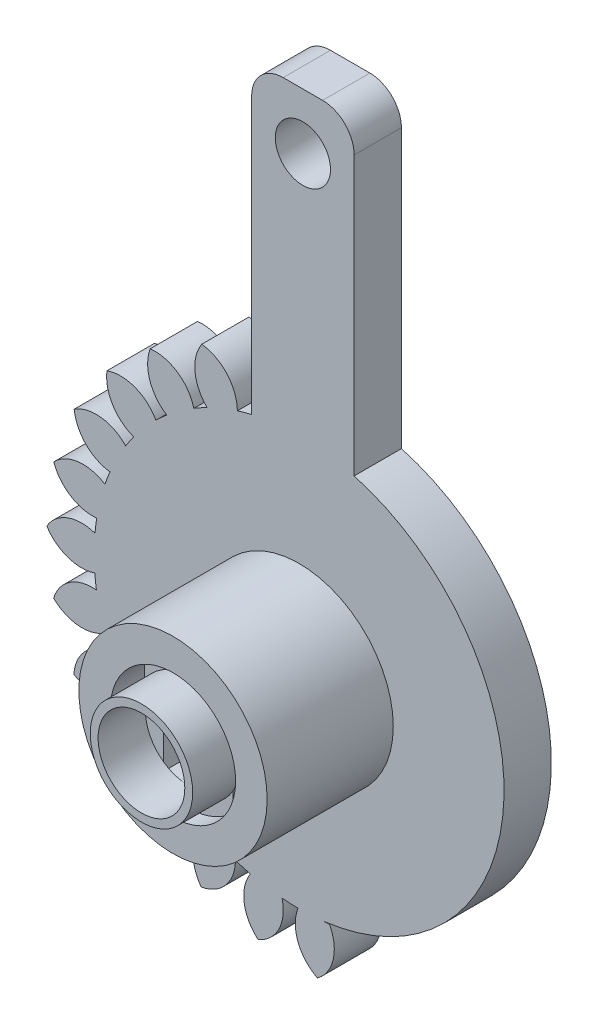
SolidWorks part; units mm, degrees
ref_plane "Front Plane" through (0, 0, 0) normal (0, 0, 1) x (1, 0, 0)
ref_plane "Top Plane" through (0, 0, 0) normal (0, 1, 0) x (1, 0, 0)
ref_plane "Right Plane" through (0, 0, 0) normal (1, 0, 0) x (0, 0, -1)
ref_plane "Plane1" through (0, 0, 5) normal (0, 0, 1) x (1, 0, 0)
ref_plane "Plane2" through (0, 0, 8) normal (0, 0, 1) x (1, 0, 0)
ref_plane "Plane3" through (0, 0, 3) normal (0, 0, 1) x (1, 0, 0)
sketch "Sketch1" plane through (0, 0, 5) normal (0, 0, 1) x (1, 0, 0)
  circle A0 centre (0, 20.9252) radius 3.9726
  circle A1 centre (0, 20.9252) radius 5
  dimension "D1" = 10
sketch "Sketch3" plane through (0, 0, 8) normal (0, 0, 1) x (1, 0, 0)
  line L0 (-3.9726, 20.9252) -> (15.3734, 20.9252) construction
  line L1 (0, 24.8978) -> (0, 8.7425) construction
  line L3 (-1.6, 23.6752) -> (1.6, 23.6752)
  line L4 (-1.6, 23.6752) -> (-1.6, 18.1752)
  line L5 (-1.6, 18.1752) -> (1.6, 18.1752)
  line L6 (1.6, 23.6752) -> (1.6, 18.1752)
  dimension "D1" = 3.2
  dimension "D2" = 5.5
  dimension "D3" = 1.6
  dimension "D4" = 2.75
extrude "Boss-Extrude1" add sketch "Sketch1" along normal blind 9 contours A0
shell "Shell1" thickness 2 removed face at (3.9726, 20.9252, 14) outward yes
extrude "Boss-Extrude2" add sketch "Sketch3" along normal blind 5 separate body
shell "Shell2" thickness 1.2 removed face at (0, 20.9252, 13) outward yes
sketch "Sketch7" plane through (0, 0, 3) normal (0, 0, -1) x (-1, 0, 0)
  line L0 (0, 14.9526) -> (0, 35.2199) construction
  line L1 (5.9726, 20.9252) -> (-26.894, 20.9252) construction
  circle A0 centre (0, 20.9252) radius 5.9726 construction
sketch "Sketch5" plane through (0, 0, 3) normal (0, 0, 1) x (1, 0, 0)
  line L1 (0, 14.9526) -> (0, 35.2199) construction
  line L2 (-5.9726, 20.9252) -> (26.894, 20.9252) construction
  circle A0 centre (0, 20.9252) radius 13
extrude "Boss-Extrude3" add sketch "Sketch5" along normal blind 3 contours A0
sketch "Sketch6" plane through (0, 0, 3) normal (0, 0, 1) x (1, 0, 0)
  line L1 (-3.01, 33.0817) -> (3.49, 33.0817)
  line L2 (-3.01, 33.0817) -> (-3.01, 53.0817)
  line L3 (-3.01, 53.0817) -> (3.49, 53.0817)
  line L4 (3.49, 33.0817) -> (3.49, 53.0817)
  dimension "D1" = 20
  dimension "D2" = 6.5
extrude "Boss-Extrude4" add sketch "Sketch6" along normal up to surface (3 mm away) up to face at (5.9726, 20.9252, 6)
sketch "Sketch8" plane through (0, 0, 3) normal (0, 0, 1) x (1, 0, 0)
  line L0 (-5.7594, 32.4645) -> (-3.9194, 33.1775)
  line L1 (0.24, 53.0817) -> (0.24, -3.388) construction
  line L2 (3.49, 53.0817) -> (-3.01, 53.0817) construction
  line L3 (13, 20.9252) -> (-7.0281, 20.9252) construction
  line L20 (-8.2588, 30.7699) -> (-6.6328, 31.8881)
  line L21 (-10.3, 28.5446) -> (-8.9758, 30.0076)
  line L22 (-11.7731, 25.9085) -> (-10.8219, 27.6375)
  line L23 (-12.5985, 23.0038) -> (-12.0717, 24.9055)
  line L24 (-12.7318, 19.987) -> (-12.6577, 21.9589)
  line L25 (-12.1657, 17.0208) -> (-12.5485, 18.9567)
  line L26 (-10.9309, 14.2651) -> (-11.7498, 16.0605)
  line L27 (-9.0939, 11.8684) -> (-10.3047, 13.4266)
  line L28 (-6.7536, 9.96) -> (-8.2911, 11.197)
  line L29 (-4.0364, 8.6427) -> (-5.8177, 9.4918)
  line L30 (-1.0886, 7.9876) -> (-3.0177, 8.403)
  line L31 (1.9309, 8.03) -> (-0.042, 7.9892)
  arc A0 (-3.9194, 33.1775) -> (-6.1748, 35.8519) centre (-6.4822, 33.3045) ccw
  arc A3 (-6.1748, 35.8519) -> (-5.7594, 32.4645) centre (-4.0035, 34.399) ccw
  arc A4 (-3.01, 33.572) -> (3.49, 33.448) centre (0, 20.9252) ccw construction
  arc A53 (-6.6328, 31.8881) -> (-9.4442, 33.9702) centre (-9.1558, 31.4205) ccw
  arc A54 (-9.4442, 33.9702) -> (-8.2588, 30.7699) centre (-6.9964, 33.0572) ccw
  arc A55 (-8.9758, 30.0076) -> (-12.1916, 31.3853) centre (-11.323, 28.9708) ccw
  arc A56 (-12.1916, 31.3853) -> (-10.3, 28.5446) centre (-9.5992, 31.0614) ccw
  arc A57 (-10.8219, 27.6375) -> (-14.2687, 28.2364) centre (-12.8667, 26.0873) ccw
  arc A58 (-14.2687, 28.2364) -> (-11.7731, 25.9085) centre (-11.6715, 28.5191) ccw
  arc A59 (-12.0717, 24.9055) -> (-15.5637, 24.6934) centre (-13.7039, 22.9256) ccw
  arc A60 (-15.5637, 24.6934) -> (-12.5985, 23.0038) centre (-13.1017, 25.5674) ccw
  arc A61 (-12.6577, 21.9589) -> (-16.0067, 20.9472) centre (-13.7893, 19.656) ccw
  arc A62 (-16.0067, 20.9472) -> (-12.7318, 19.987) centre (-13.8126, 22.3655) ccw
  arc A63 (-12.5485, 18.9567) -> (-15.5739, 17.1999) centre (-13.1185, 16.4548) ccw
  arc A64 (-15.5739, 17.1999) -> (-12.1657, 17.0208) centre (-13.766, 19.0859) ccw
  arc A65 (-11.7498, 16.0605) -> (-14.2885, 13.6534) centre (-11.7274, 13.4946) ccw
  arc A66 (-14.2885, 13.6534) -> (-10.9309, 14.2651) centre (-12.9643, 15.9055) ccw
  arc A67 (-10.3047, 13.4266) -> (-12.2199, 10.4989) centre (-9.6912, 10.9351) ccw
  arc A68 (-12.2199, 10.4989) -> (-9.0939, 11.8684) centre (-11.4507, 12.9957) ccw
  arc A69 (-8.2911, 11.197) -> (-9.4795, 7.9065) centre (-7.1197, 8.9141) ccw
  arc A70 (-9.4795, 7.9065) -> (-6.7536, 9.96) centre (-9.3069, 10.5134) ccw
  arc A71 (-5.8177, 9.4918) -> (-6.2152, 6.016) centre (-4.1513, 7.5406) ccw
  arc A72 (-6.2152, 6.016) -> (-4.0364, 8.6427) centre (-6.6484, 8.5924) ccw
  arc A73 (-3.0177, 8.403) -> (-2.6029, 4.9292) centre (-0.9462, 6.8887) ccw
  arc A74 (-2.6029, 4.9292) -> (-1.0886, 7.9876) centre (-3.6186, 7.3362) ccw
  arc A75 (-0.042, 7.9892) -> (1.1627, 4.7047) centre (2.3228, 6.9935) ccw
  arc A76 (1.1627, 4.7047) -> (1.9309, 8.03) centre (-0.3808, 6.8127) ccw
  point P26 (0.24, 20.9252)
  point P78 (0.24, 20.9252)
  point P153 (0.24, 20.9252)
  dimension "D1" = 13
extrude "Boss-Extrude5" add sketch "Sketch8" along normal up to surface (3 mm away) up to face at (3.9726, 20.9252, 6)
sketch "Sketch9" plane through (0, 0, 3) normal (0, 0, -1) x (-1, 0, 0)
  line L0 (-0.24, 53.0817) -> (-0.24, 49.0919) construction
  line L1 (-3.49, 53.0817) -> (3.01, 53.0817) construction
  circle A0 centre (-0.24, 49.5317) radius 1.75
  dimension "D1" = 3.55
extrude "Cut-Extrude1" cut sketch "Sketch9" against normal up to surface (3 mm away) up to face at (3.9726, 20.9252, 6)
fillet "Fillet1" radius 2 2 edges at (3.49, 53.0817, 4.5) (-3.01, 53.0817, 4.5)
sketch "Sketch11" plane through (0, 0, 13) normal (0, 0, 1) x (1, 0, 0)
  circle A0 centre (0, 20.9354) radius 2.75
  circle A1 centre (0, 20.9354) radius 3.25
extrude "Boss-Extrude7" add sketch "Sketch11" along normal blind 3
